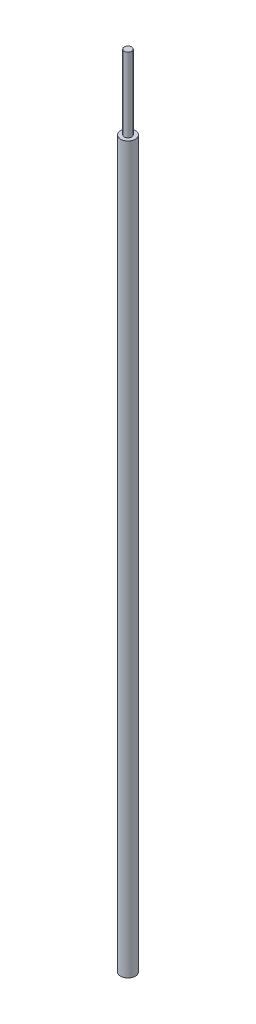
SolidWorks part; units mm, degrees
material "S-Glass Fiber"
ref_plane "Front Plane" through (0, 0, 0) normal (0, 0, 1) x (1, 0, 0)
ref_plane "Top Plane" through (0, 0, 0) normal (0, 1, 0) x (1, 0, 0)
ref_plane "Right Plane" through (0, 0, 0) normal (1, 0, 0) x (0, 0, -1)
sketch "Sketch1" plane through (0, 0, 0) normal (0, 1, 0) x (1, 0, 0)
  circle A0 centre (0, 0) radius 0.2
  dimension "D1" = 0.4
extrude "Boss-Extrude1" add sketch "Sketch1" along normal blind 19.5
sketch "Sketch2" plane through (0, 19.5, 0) normal (0, 1, 0) x (1, 0, 0)
  circle A0 centre (0, 0) radius 0.1
  dimension "D1" = 0.2
extrude "Boss-Extrude2" add sketch "Sketch2" along normal blind 2
ref_axis "Axis1" through (0, 21.5, 0) along (0, -1, 0)
sketch "Sketch3" plane through (0, 21.5, 0) normal (0, 1, 0) x (1, 0, 0)
  line L0 (0, 0) -> (0.267, 0) construction
